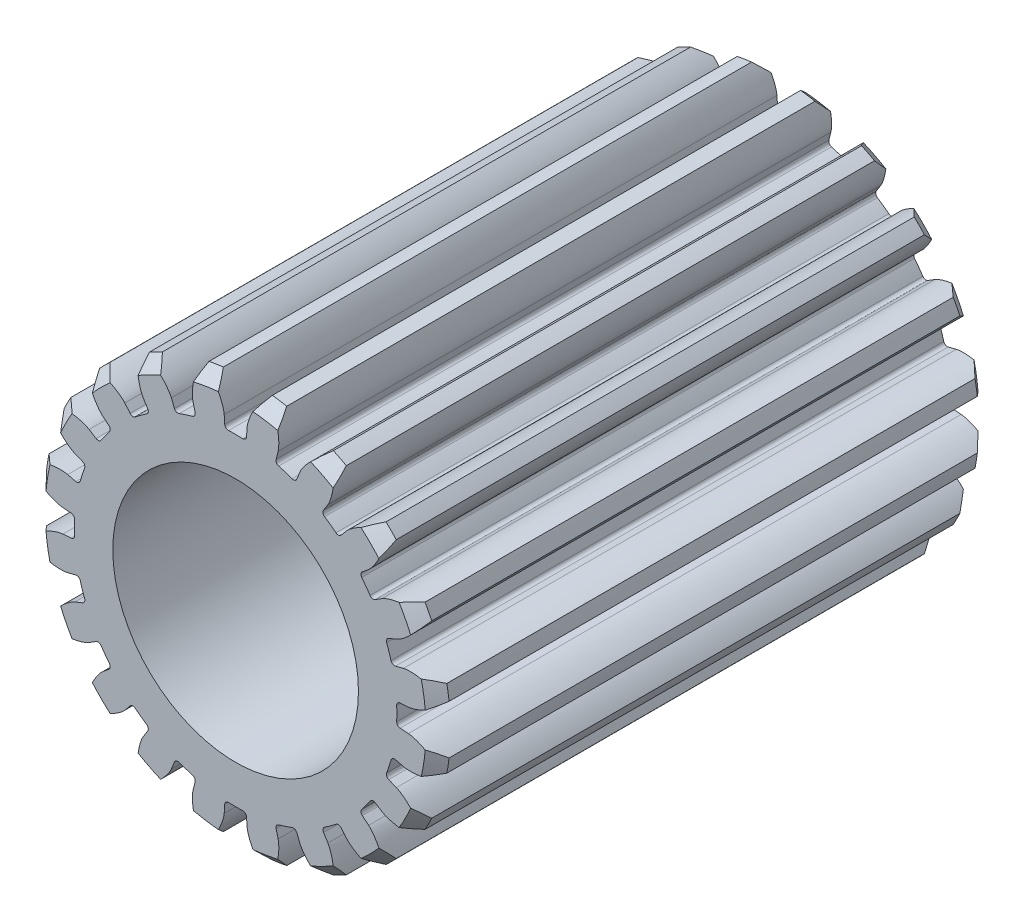
SolidWorks part; units mm, degrees
ref_plane "中间平面" through (0, 0, 0) normal (0, 0, 1) x (1, 0, 0)
ref_plane "上视基准面" through (0, 0, 0) normal (0, 1, 0) x (1, 0, 0)
ref_plane "右视基准面" through (0, 0, 0) normal (1, 0, 0) x (0, 0, -1)
sketch "直齿轮" plane through (0, 0, 0) normal (0, 0, 1) x (1, 0, 0)
  line L0 (0, 0) -> (-1.1769, 14.9538) construction
  line L2 (-0.931, 14.0646) -> (0, 0)
  line L3 (0, 0) -> (0, 52) construction
  line L4 (1.1769, 14.9538) -> (0, 0) construction
  line L6 (0, 0) -> (0.931, 14.0646)
  circle A0 centre (0, 0) radius 14.0954
  circle A1 centre (0, 0) radius 13.125
  arc A2 (1.1769, 14.9538) -> (-1.1769, 14.9538) centre (0, 0) ccw
  circle A3 centre (0, 0) radius 16.5
  spline S0 degree 4 poles (-0.931, 14.0646) (-0.9327, 14.0914) (-0.9379, 14.1447) (-0.9547, 14.2507) (-0.9993, 14.4498) (-1.079, 14.7121) (-1.2678, 15.1967) (-1.6539, 15.9283) (-2.301, 16.8363) (-3.3778, 17.9621) (-4.8228, 19.0782) (-6.5698, 20.0635) (-8.5805, 20.8551) (-10.6724, 21.3918) (-12.8109, 21.6889) (-15.0748, 21.7642) (-17.8728, 21.5649) (-21.1566, 20.9008) (-24.82, 19.5802) (-28.6136, 17.502) (-32.0674, 14.9013) (-34.7537, 12.2396) (-36.7975, 9.7294) (-38.3221, 7.5071) (-39.4327, 5.659) (-40.6829, 3.2718) (-41.7475, 0.7937) (-42.6252, -1.7556) (-43.4549, -4.8816) (-43.9102, -7.2641) (-44.1864, -9.4046) (-44.3332, -11.2817) (-44.3828, -12.2291) (-44.4091, -13.0247) (-44.4196, -13.7585) (-44.4222, -14.3265) (-44.4104, -15.1362) (-44.3924, -15.7384) (-44.3483, -16.7302) (-44.293, -17.491) (-44.216, -18.4224) (-44.1254, -19.2462) (-44.0164, -20.1361) (-43.8923, -20.976) (-43.7862, -21.6356) (-43.7107, -22.0538) (-43.6714, -22.2717) knots 0 0 0 0 0 0.001401 0.002802 0.005604 0.010661 0.015718 0.02996 0.048734 0.068727 0.096889 0.125051 0.153212 0.181374 0.209535 0.237696 0.271429 0.327752 0.384075 0.440398 0.496721 0.553044 0.581206 0.609367 0.637529 0.66569 0.722013 0.750174 0.778336 0.834659 0.84874 0.86282 0.876901 0.883942 0.890982 0.900036 0.909091 0.920455 0.931818 0.943182 0.954545 0.965909 0.977273 0.988636 1 1 1 1 1 construction
  spline S1 degree 4 poles (-0.931, 14.0646) (-0.9327, 14.0914) (-0.9379, 14.1447) (-0.9547, 14.2507) (-0.9993, 14.4498) (-1.079, 14.7121) (-1.2678, 15.1967) (-1.6539, 15.9283) (-2.301, 16.8363) (-3.3778, 17.9621) (-4.8228, 19.0782) (-6.5698, 20.0635) (-8.5805, 20.8551) (-10.6724, 21.3918) (-12.8109, 21.6889) (-15.0748, 21.7642) (-17.8728, 21.5649) (-21.1566, 20.9008) (-24.82, 19.5802) (-28.6136, 17.502) (-32.0674, 14.9013) (-34.7537, 12.2396) (-36.7975, 9.7294) (-38.3221, 7.5071) (-39.4327, 5.659) (-40.6829, 3.2718) (-41.7475, 0.7937) (-42.6252, -1.7556) (-43.4549, -4.8816) (-43.9102, -7.2641) (-44.1864, -9.4046) (-44.3332, -11.2817) (-44.3828, -12.2291) (-44.4091, -13.0247) (-44.4196, -13.7585) (-44.4222, -14.3265) (-44.4141, -14.8842) (-44.4069, -15.2031) (-44.4025, -15.3605) knots 0 0 0 0 0 0.001401 0.002802 0.005604 0.010661 0.015718 0.02996 0.048734 0.068727 0.096889 0.125051 0.153212 0.181374 0.209535 0.237696 0.271429 0.327752 0.384075 0.440398 0.496721 0.553044 0.581206 0.609367 0.637529 0.66569 0.722013 0.750174 0.778336 0.834659 0.84874 0.86282 0.876901 0.883942 0.890982 0.900036 0.909091 0.909091 0.909091 0.909091 0.909091
  spline S2 degree 4 poles (0.931, 14.0646) (0.9327, 14.0914) (0.9379, 14.1447) (0.9547, 14.2507) (0.9993, 14.4498) (1.079, 14.7121) (1.2678, 15.1967) (1.6539, 15.9283) (2.301, 16.8363) (3.3778, 17.9621) (4.8228, 19.0782) (6.5698, 20.0635) (8.5805, 20.8551) (10.6724, 21.3918) (12.8109, 21.6889) (15.0748, 21.7642) (17.8728, 21.5649) (21.1566, 20.9008) (24.82, 19.5802) (28.6136, 17.502) (32.0674, 14.9013) (34.7537, 12.2396) (36.7975, 9.7294) (38.3221, 7.5071) (39.4327, 5.659) (40.6829, 3.2718) (41.7475, 0.7937) (42.6252, -1.7556) (43.4549, -4.8816) (43.9102, -7.2641) (44.1864, -9.4046) (44.3332, -11.2817) (44.3828, -12.2291) (44.4091, -13.0247) (44.4196, -13.7585) (44.4222, -14.3265) (44.4104, -15.1362) (44.3924, -15.7384) (44.3483, -16.7302) (44.293, -17.491) (44.216, -18.4224) (44.1254, -19.2462) (44.0164, -20.1361) (43.8923, -20.976) (43.7862, -21.6356) (43.7107, -22.0538) (43.6714, -22.2717) knots 0 0 0 0 0 0.001401 0.002802 0.005604 0.010661 0.015718 0.02996 0.048734 0.068727 0.096889 0.125051 0.153212 0.181374 0.209535 0.237696 0.271429 0.327752 0.384075 0.440398 0.496721 0.553044 0.581206 0.609367 0.637529 0.66569 0.722013 0.750174 0.778336 0.834659 0.84874 0.86282 0.876901 0.883942 0.890982 0.900036 0.909091 0.920455 0.931818 0.943182 0.954545 0.965909 0.977273 0.988636 1 1 1 1 1 construction
  spline S3 degree 4 poles (0.931, 14.0646) (0.9327, 14.0914) (0.9379, 14.1447) (0.9547, 14.2507) (0.9993, 14.4498) (1.079, 14.7121) (1.2678, 15.1967) (1.6539, 15.9283) (2.301, 16.8363) (3.3778, 17.9621) (4.8228, 19.0782) (6.5698, 20.0635) (8.5805, 20.8551) (10.6724, 21.3918) (12.8109, 21.6889) (15.0748, 21.7642) (17.8728, 21.5649) (21.1566, 20.9008) (24.82, 19.5802) (28.6136, 17.502) (32.0674, 14.9013) (34.7537, 12.2396) (36.7975, 9.7294) (38.3221, 7.5071) (39.4327, 5.659) (40.6829, 3.2718) (41.7475, 0.7937) (42.6252, -1.7556) (43.4549, -4.8816) (43.9102, -7.2641) (44.1864, -9.4046) (44.3332, -11.2817) (44.3828, -12.2291) (44.4091, -13.0247) (44.4196, -13.7585) (44.4222, -14.3265) (44.4141, -14.8842) (44.4069, -15.2031) (44.4025, -15.3605) knots 0 0 0 0 0 0.001401 0.002802 0.005604 0.010661 0.015718 0.02996 0.048734 0.068727 0.096889 0.125051 0.153212 0.181374 0.209535 0.237696 0.271429 0.327752 0.384075 0.440398 0.496721 0.553044 0.581206 0.609367 0.637529 0.66569 0.722013 0.750174 0.778336 0.834659 0.84874 0.86282 0.876901 0.883942 0.890982 0.900036 0.909091 0.909091 0.909091 0.909091 0.909091
  dimension "基圆直径" = 28.1908
  dimension "齿根圆" = 26.25
  dimension "分度圆" = 30
  dimension "齿顶圆" = 33
  dimension "D1" = 2.3562
sketch "圆" plane through (0, 0, 0) normal (0, 0, 1) x (1, 0, 0)
  circle A0 centre (0, 0) radius 16.5 construction
  circle A1 centre (0, 0) radius 16.5
extrude "毛胚" add sketch "圆" along normal mid plane 45
chamfer "轮齿倒角" distance 1 angle 45 2 edges at (16.5, 0, -22.5) (16.5, 0, 22.5)
sketch "齿形" plane through (0, 0, 0) normal (0, 0, 1) x (1, 0, 0)
  line L4 (0, 0) -> (0.931, 14.0646) construction
  line L5 (-0.931, 14.0646) -> (0, 0) construction
  line L6 (0, 0) -> (0.931, 14.0646)
  line L7 (-0.931, 14.0646) -> (0, 0)
  circle A4 centre (0, 0) radius 13.125 construction
  circle A5 centre (0, 0) radius 16.5 construction
  circle A6 centre (0, 0) radius 13.125
  circle A7 centre (0, 0) radius 16.5
  spline S1 degree 4 poles (-998.7152, 36.9546) (28.6673, 8.9334) (1.4968, 11.3937) (0.6713, 12.9835) (0.9993, 14.4498) (1.079, 14.7121) (1.2678, 15.1967) (1.6539, 15.9283) (2.301, 16.8363) (3.3778, 17.9621) (4.8228, 19.0782) (6.5698, 20.0635) (8.5805, 20.8551) (10.6724, 21.3918) (12.8109, 21.6889) (15.0748, 21.7642) (17.8728, 21.5649) (21.1566, 20.9008) (24.82, 19.5802) (28.6136, 17.502) (32.0674, 14.9013) (34.7537, 12.2396) (36.7975, 9.7294) (38.3221, 7.5071) (39.4327, 5.659) (40.6829, 3.2718) (41.7475, 0.7937) (42.6252, -1.7556) (43.4549, -4.8816) (43.9102, -7.2641) (44.1864, -9.4046) (44.3332, -11.2817) (44.3828, -12.2291) (44.4091, -13.0247) (44.4196, -13.7585) (44.4315, -16.3046) (44.1383, -22.1184) (45.0744, 21.9799) (15.4643, -1014.9401) knots -0.067838 -0.067838 -0.067838 -0.067838 -0.067838 0.001401 0.002802 0.005604 0.010661 0.015718 0.02996 0.048734 0.068727 0.096889 0.125051 0.153212 0.181374 0.209535 0.237696 0.271429 0.327752 0.384075 0.440398 0.496721 0.553044 0.581206 0.609367 0.637529 0.66569 0.722013 0.750174 0.778336 0.834659 0.84874 0.86282 0.876901 0.883942 0.890982 0.900036 1.021187 1.021187 1.021187 1.021187 1.021187 only from (0.931, 14.0646) to (44.4025, -15.3605) construction
  spline S3 degree 4 poles (998.7152, 36.9546) (-28.6673, 8.9334) (-1.4968, 11.3937) (-0.6713, 12.9835) (-0.9993, 14.4498) (-1.079, 14.7121) (-1.2678, 15.1967) (-1.6539, 15.9283) (-2.301, 16.8363) (-3.3778, 17.9621) (-4.8228, 19.0782) (-6.5698, 20.0635) (-8.5805, 20.8551) (-10.6724, 21.3918) (-12.8109, 21.6889) (-15.0748, 21.7642) (-17.8728, 21.5649) (-21.1566, 20.9008) (-24.82, 19.5802) (-28.6136, 17.502) (-32.0674, 14.9013) (-34.7537, 12.2396) (-36.7975, 9.7294) (-38.3221, 7.5071) (-39.4327, 5.659) (-40.6829, 3.2718) (-41.7475, 0.7937) (-42.6252, -1.7556) (-43.4549, -4.8816) (-43.9102, -7.2641) (-44.1864, -9.4046) (-44.3332, -11.2817) (-44.3828, -12.2291) (-44.4091, -13.0247) (-44.4196, -13.7585) (-44.4315, -16.3046) (-44.1383, -22.1184) (-45.0744, 21.9799) (-15.4643, -1014.9401) knots -0.067838 -0.067838 -0.067838 -0.067838 -0.067838 0.001401 0.002802 0.005604 0.010661 0.015718 0.02996 0.048734 0.068727 0.096889 0.125051 0.153212 0.181374 0.209535 0.237696 0.271429 0.327752 0.384075 0.440398 0.496721 0.553044 0.581206 0.609367 0.637529 0.66569 0.722013 0.750174 0.778336 0.834659 0.84874 0.86282 0.876901 0.883942 0.890982 0.900036 1.021187 1.021187 1.021187 1.021187 1.021187 only from (-0.931, 14.0646) to (-44.4025, -15.3605) construction
  spline S4 degree 4 poles (0.931, 14.0646) (0.9327, 14.0914) (0.9379, 14.1447) (0.9547, 14.2507) (0.9993, 14.4498) (1.079, 14.7121) (1.2678, 15.1967) (1.6539, 15.9283) (2.301, 16.8363) (3.3778, 17.9621) (4.8228, 19.0782) (6.5698, 20.0635) (8.5805, 20.8551) (10.6724, 21.3918) (12.8109, 21.6889) (15.0748, 21.7642) (17.8728, 21.5649) (21.1566, 20.9008) (24.82, 19.5802) (28.6136, 17.502) (32.0674, 14.9013) (34.7537, 12.2396) (36.7975, 9.7294) (38.3221, 7.5071) (39.4327, 5.659) (40.6829, 3.2718) (41.7475, 0.7937) (42.6252, -1.7556) (43.4549, -4.8816) (43.9102, -7.2641) (44.1864, -9.4046) (44.3332, -11.2817) (44.3828, -12.2291) (44.4091, -13.0247) (44.4196, -13.7585) (44.4222, -14.3265) (44.4141, -14.8842) (44.4069, -15.2031) (44.4025, -15.3605) knots 0 0 0 0 0 0.001401 0.002802 0.005604 0.010661 0.015718 0.02996 0.048734 0.068727 0.096889 0.125051 0.153212 0.181374 0.209535 0.237696 0.271429 0.327752 0.384075 0.440398 0.496721 0.553044 0.581206 0.609367 0.637529 0.66569 0.722013 0.750174 0.778336 0.834659 0.84874 0.86282 0.876901 0.883942 0.890982 0.900036 0.909091 0.909091 0.909091 0.909091 0.909091
  spline S5 degree 4 poles (-0.931, 14.0646) (-0.9327, 14.0914) (-0.9379, 14.1447) (-0.9547, 14.2507) (-0.9993, 14.4498) (-1.079, 14.7121) (-1.2678, 15.1967) (-1.6539, 15.9283) (-2.301, 16.8363) (-3.3778, 17.9621) (-4.8228, 19.0782) (-6.5698, 20.0635) (-8.5805, 20.8551) (-10.6724, 21.3918) (-12.8109, 21.6889) (-15.0748, 21.7642) (-17.8728, 21.5649) (-21.1566, 20.9008) (-24.82, 19.5802) (-28.6136, 17.502) (-32.0674, 14.9013) (-34.7537, 12.2396) (-36.7975, 9.7294) (-38.3221, 7.5071) (-39.4327, 5.659) (-40.6829, 3.2718) (-41.7475, 0.7937) (-42.6252, -1.7556) (-43.4549, -4.8816) (-43.9102, -7.2641) (-44.1864, -9.4046) (-44.3332, -11.2817) (-44.3828, -12.2291) (-44.4091, -13.0247) (-44.4196, -13.7585) (-44.4222, -14.3265) (-44.4141, -14.8842) (-44.4069, -15.2031) (-44.4025, -15.3605) knots 0 0 0 0 0 0.001401 0.002802 0.005604 0.010661 0.015718 0.02996 0.048734 0.068727 0.096889 0.125051 0.153212 0.181374 0.209535 0.237696 0.271429 0.327752 0.384075 0.440398 0.496721 0.553044 0.581206 0.609367 0.637529 0.66569 0.722013 0.750174 0.778336 0.834659 0.84874 0.86282 0.876901 0.883942 0.890982 0.900036 0.909091 0.909091 0.909091 0.909091 0.909091
extrude "插齿" cut sketch "齿形" against normal mid plane 45 contours S5 A6 S4 A7 region at (0, 15.05, 0)
fillet "圆角1" [suppressed] radius 0.3
pattern_circular "圆周阵列1" [suppressed] count 20 over 360 of bodies 165
fillet "圆角2" radius 0.3 2 edges at (0.8669, 13.0963, 0) (-0.8669, 13.0963, 0)
pattern_circular "圆周阵列2" count 20 over 360 about axis through (0, 0, 22.5) along (0, 0, -1) of "圆角2", "插齿"
sketch "分度圆" plane through (0, 0, 0) normal (0, 0, 1) x (1, 0, 0)
  circle A0 centre (0, 0) radius 15 construction
  circle A1 centre (0, 0) radius 15 construction
sketch "草图1" plane through (0, 0, 22.5) normal (0, 0, 1) x (1, 0, 0)
  circle A0 centre (0, 0) radius 10
  dimension "D1" = 20
extrude "切除-拉伸1" cut sketch "草图1" against normal through all
equation "\"m\"= 1.5'模数"
equation "\"z\" = 20'齿数"
equation "\"a\"= 20'压力角（常见为20°）"
equation "\"B\" = 45'齿宽"
equation "\"C1\"= 1'轮齿倒角（若设为0，则无倒角）"
equation "\"x\"= 0'变位系数（不懂勿动）"
equation "\"ha\"= 1'齿顶高系数（不懂勿动）"
equation "\"c\"= 0.25'顶隙系数（不懂勿动）"
equation "\"基圆直径@直齿轮\"= \"m\" * \"z\" * cos ( \"a\" )"
equation "\"齿根圆@直齿轮\" = \"m\" * ( \"z\" - 2 * ( \"ha\" - \"x\" + \"c\" ) )"
equation "\"分度圆@直齿轮\"=\"m\" * \"z\""
equation "\"齿顶圆@直齿轮\" = \"m\" * ( \"z\" + 2 * ( \"ha\" + \"x\" ) )"
equation "\"R\"= 0.3'齿根圆角"
equation "\"D1\"= \"R\""
equation "\"D1@毛胚\" = \"B\""
equation "\"D1@轮齿倒角\" = IIF ( \"C1\" > 0 , \"C1\" , 0.001 )"
equation "\"轮齿倒角\"= IIF ( \"C1\" > 0 , \"unsuppressed\" , \"suppressed\" )"
equation "\"D1@插齿\" = \"B\""
equation "\"D1@圆周阵列1\" = \"z\""
equation "\"D1@直齿轮\"= \"m\" * ( pi / 2 ) - 2 * \"m\" * tan ( \"a\" ) * \"x\"'作者：机械菌-"
equation "\"D1@圆角1\"=\"R\""
equation "\"圆角1\" = IIF ( \"m\" * ( \"z\" - 2 * ( \"ha\" - \"x\" + \"c\" ) ) > \"m\" * \"z\" * cos ( \"a\" ) , \"unsuppressed\" , \"suppressed\" )"
equation "\"圆周阵列1\"= IIF ( \"m\" * ( \"z\" - 2 * ( \"ha\" - \"x\" + \"c\" ) ) > \"m\" * \"z\" * cos ( \"a\" ) , \"unsuppressed\" , \"suppressed\" )"
equation "\"D1@圆角2\"=\"R\""
equation "\"D1@圆周阵列2\" = \"z\""
equation "\"圆角2\" = IIF ( \"m\" * ( \"z\" - 2 * ( \"ha\" - \"x\" + \"c\" ) ) < \"m\" * \"z\" * cos ( \"a\" ) , \"unsuppressed\" , \"suppressed\" )"
equation "\"圆周阵列2\"= IIF ( \"m\" *  ( \"z\" - 2 *  ( \"ha\" - \"x\" + \"c\" )  )  < \"m\" * \"z\" * cos ( \"a\" )  ,  unsuppressed  ,  suppressed  ) "
